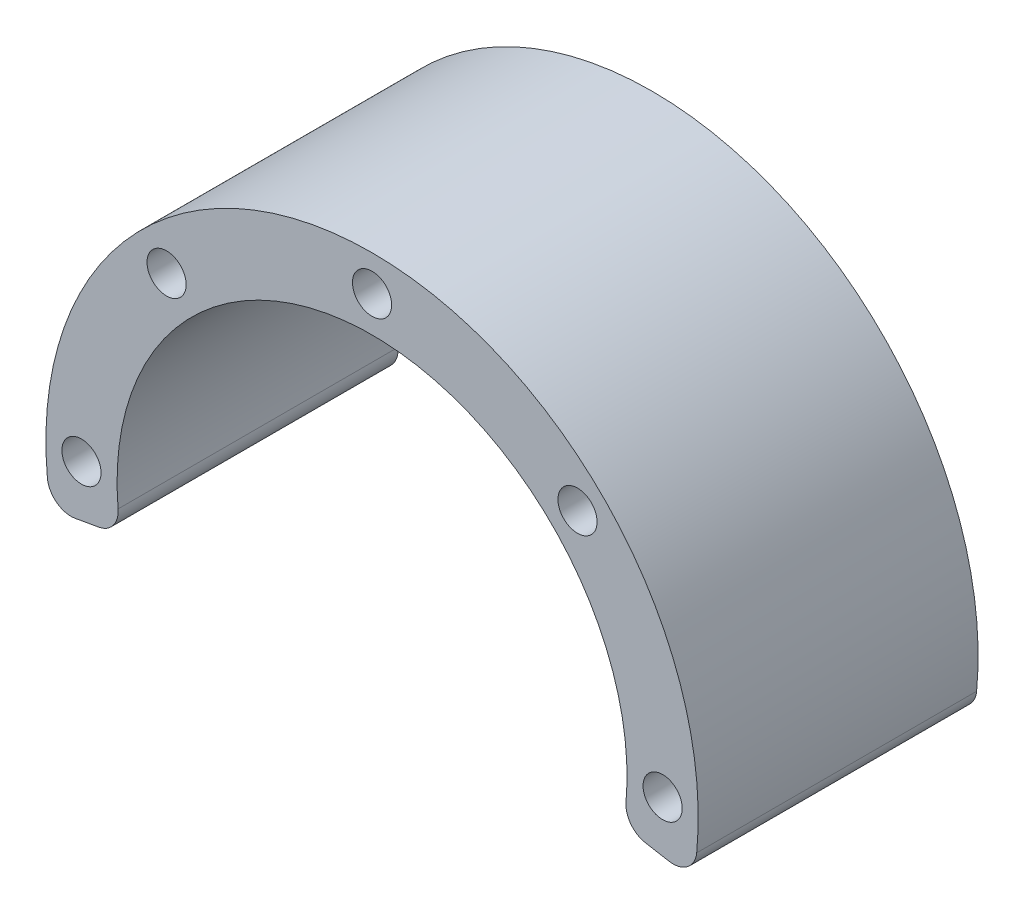
SolidWorks part; units mm, degrees
material "ABS"
ref_plane "前视基准面" through (0, 0, 0) normal (0, 0, 1) x (1, 0, 0)
ref_plane "上视基准面" through (0, 0, 0) normal (0, 1, 0) x (1, 0, 0)
ref_plane "右视基准面" through (0, 0, 0) normal (1, 0, 0) x (0, 0, -1)
sketch "草图1" plane through (0, 0, 0) normal (0, 0, 1) x (1, 0, 0)
  circle A0 centre (0, 0) radius 8.05
  circle A1 centre (0, 0) radius 21 construction
  circle A2 centre (0, 0) radius 27.5
  dimension "D1" = 16.1
  dimension "D2" = 42
  dimension "D3" = 6.5
extrude "凸台-拉伸1" add sketch "草图1" along normal blind 2
sketch "草图2" plane through (0, 0, 2) normal (0, 0, 1) x (1, 0, 0)
  circle A0 centre (0, 0) radius 11 construction
  circle A1 centre (0, 11) radius 1.525
  circle A2 centre (9.5263, 5.5) radius 1.525
  circle A3 centre (9.5263, -5.5) radius 1.525
  circle A4 centre (0, -11) radius 1.525
  circle A5 centre (-9.5263, -5.5) radius 1.525
  circle A6 centre (-9.5263, 5.5) radius 1.525
  point P29 (0, 0)
  dimension "D1" = 22
  dimension "D2" = 3.05
  dimension "D3" = 6
extrude "切除-拉伸1" cut sketch "草图2" against normal blind 2
sketch "草图3" plane through (0, 0, 2) normal (0, 0, 1) x (1, 0, 0)
  circle A0 centre (0, 0) radius 24.5 construction
  circle A1 centre (0, 0) radius 27.5 construction
  circle A2 centre (0, 24.5) radius 1.65
  circle A3 centre (17.3241, 17.3241) radius 1.65
  circle A4 centre (24.5, 0) radius 1.65
  circle A5 centre (17.3241, -17.3241) radius 1.65
  circle A6 centre (0, -24.5) radius 1.65
  circle A7 centre (-17.3241, -17.3241) radius 1.65
  circle A8 centre (-24.5, 0) radius 1.65
  circle A9 centre (-17.3241, 17.3241) radius 1.65
  point P31 (0, 0)
  dimension "D1" = 3
  dimension "D2" = 3.3
  dimension "D3" = 8
extrude "切除-拉伸2" cut sketch "草图3" against normal blind 2
sketch "草图4" plane through (0, 0, 2) normal (0, 0, 1) x (1, 0, 0)
  circle A0 centre (0, 0) radius 21.5
  dimension "D1" = 43
extrude "切除-拉伸3" cut sketch "草图4" against normal blind 10
sketch "草图5" plane through (0, 0, 0) normal (0, 0, -1) x (-1, 0, 0)
  circle A0 centre (0, 24.5) radius 1.65 construction
  circle A1 centre (0, 0) radius 27.5
  circle A2 centre (0, 0) radius 27.5
  circle A3 centre (0, 24.5) radius 1.65
  circle A4 centre (17.3241, 17.3241) radius 1.65 construction
  circle A5 centre (24.5, 0) radius 1.65 construction
  circle A6 centre (17.3241, -17.3241) radius 1.65 construction
  circle A7 centre (0, -24.5) radius 1.65 construction
  circle A8 centre (-17.3241, -17.3241) radius 1.65 construction
  circle A9 centre (-24.5, 0) radius 1.65 construction
  circle A10 centre (0, 0) radius 21.5 construction
  circle A11 centre (-17.3241, 17.3241) radius 1.65 construction
  circle A12 centre (17.3241, 17.3241) radius 1.65
  circle A13 centre (24.5, 0) radius 1.65
  circle A14 centre (17.3241, -17.3241) radius 1.65
  circle A15 centre (0, -24.5) radius 1.65
  circle A16 centre (-17.3241, -17.3241) radius 1.65
  circle A17 centre (-24.5, 0) radius 1.65
  circle A18 centre (0, 0) radius 21.5
  circle A19 centre (-17.3241, 17.3241) radius 1.65
  dimension "D1" = 0
extrude "凸台-拉伸2" add sketch "草图5" against normal blind 23.6
sketch "草图6" plane through (0, 0, 23.6) normal (0, 0, 1) x (1, 0, 0)
  line L0 (21.1734, -3.7334) -> (27.0822, -4.7753)
  line L1 (0, -34.4757) -> (0, 0) construction
  line L2 (-21.1734, -3.7334) -> (-27.0822, -4.7753)
  line L3 (21.1734, -3.7334) -> (0, 0) construction
  circle A0 centre (0, 0) radius 27.5 construction
  circle A1 centre (0, 0) radius 21.5 construction
  arc A2 (-27.0822, -4.7753) -> (27.0822, -4.7753) centre (0, 0) ccw
  arc A3 (-21.1734, -3.7334) -> (21.1734, -3.7334) centre (0, 0) ccw
  dimension "D1" = 80
extrude "切除-拉伸4" cut sketch "草图6" against normal blind 23.6
fillet "圆角1" radius 2 4 edges at (27.0822, -4.7753, 11.8) (-27.0822, -4.7753, 11.8) (-21.1734, -3.7334, 11.8) (21.1734, -3.7334, 11.8)
